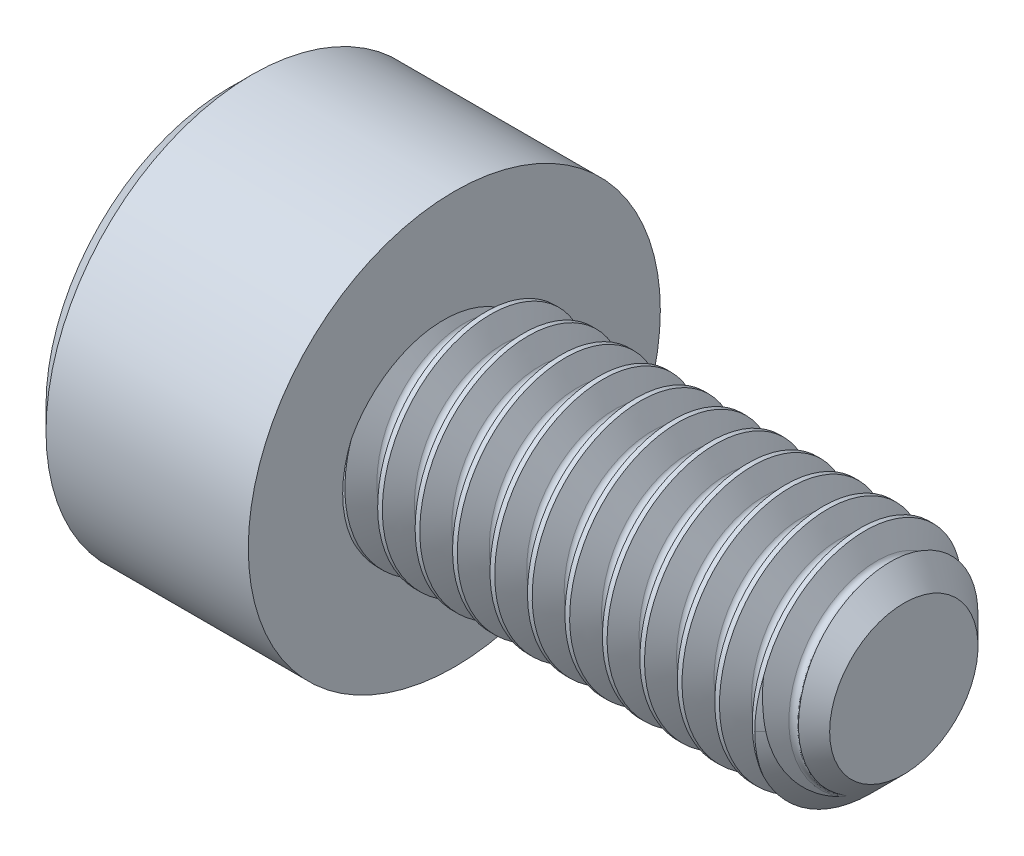
SolidWorks part; units mm, degrees
material "AISI Type 316L stainless steel"
ref_plane "Front Plane" through (0, 0, 0) normal (0, 0, 1) x (1, 0, 0)
ref_plane "Top Plane" through (0, 0, 0) normal (0, 1, 0) x (1, 0, 0)
ref_plane "Right Plane" through (0, 0, 0) normal (1, 0, 0) x (0, 0, -1)
sketch "Sketch1" plane through (0, 0, 0) normal (0, 0, 1) x (1, 0, 0)
  line L0 (-88.7055, 0) -> (96.9812, 0) construction
  line L1 (0, 0) -> (0, 2.75)
  line L2 (0, 2.75) -> (3, 2.75)
  line L4 (9, 0) -> (9, 1.49)
  line L5 (9, 1.49) -> (3, 1.49)
  line L6 (3, 1.49) -> (3, 2.75)
  line L7 (0, 0) -> (9, 0)
revolve "Revolve1" add sketch "Sketch1" angle 360 about L0
chamfer "Chamfer1" distance 0.5 angle 45 1 edges at (9, 0, 1.49)
chamfer "Chamfer2" distance 0.3 angle 45 1 edges at (0, 0, 2.75)
sketch "Sketch3" plane through (0, 0, 0) normal (1, 0, 0) x (0, 0, -1)
  line L1 (-1.4434, 0) -> (-0.7217, -1.25)
  line L2 (-0.7217, -1.25) -> (0.7217, -1.25)
  line L3 (0.7217, -1.25) -> (1.4434, 0)
  line L4 (1.4434, 0) -> (0.7217, 1.25)
  line L5 (0.7217, 1.25) -> (-0.7217, 1.25)
  line L6 (-0.7217, 1.25) -> (-1.4434, 0)
  circle A0 centre (0, 0) radius 1.25 construction
extrude "Cut-Extrude1" cut sketch "Sketch3" along normal blind 2.5
chamfer "Chamfer3" distance 0.3 angle 45 6 edges at (0, 1.25, 0) (0, 0.625, 1.0825) (0, -0.625, 1.0825) (0, -1.25, 0) (0, -0.625, -1.0825) (0, 0.625, -1.0825)
sketch "Sketch5" plane through (9, 0, 0) normal (1, 0, 0) x (0, 0, -1)
  circle A0 centre (0, 0) radius 1.49
curve "Helix/Spiral1" pitch 0.5 height 6 radius 1.49 centre (9, 0, 0) axis (-1, 0, 0) start towards (0, 0, -1)
sketch "Sketch8" plane through (0, 0, 0) normal (0, 1, 0) x (1, 0, 0)
  line L0 (9, 1.49) -> (9, 1.1111) construction
  line L1 (9.0625, 1.2194) -> (9.3281, 1.6794)
  line L2 (9.3281, 1.6794) -> (8.6719, 1.6794)
  line L3 (8.6719, 1.6794) -> (8.9375, 1.2194)
  line L4 (9, -0.99) -> (9, 0.99) construction
  circle A0 centre (9, 1.49) radius 0.1894 construction
  arc A1 (9.0625, 1.2194) -> (8.9375, 1.2194) centre (9, 1.2555) cw
  dimension "D2" = 0.0722
  dimension "D1" = 0.3789
sweep "Cut-Sweep1" cut profiles "Sketch8" path "Helix/Spiral1" align with end faces yes
